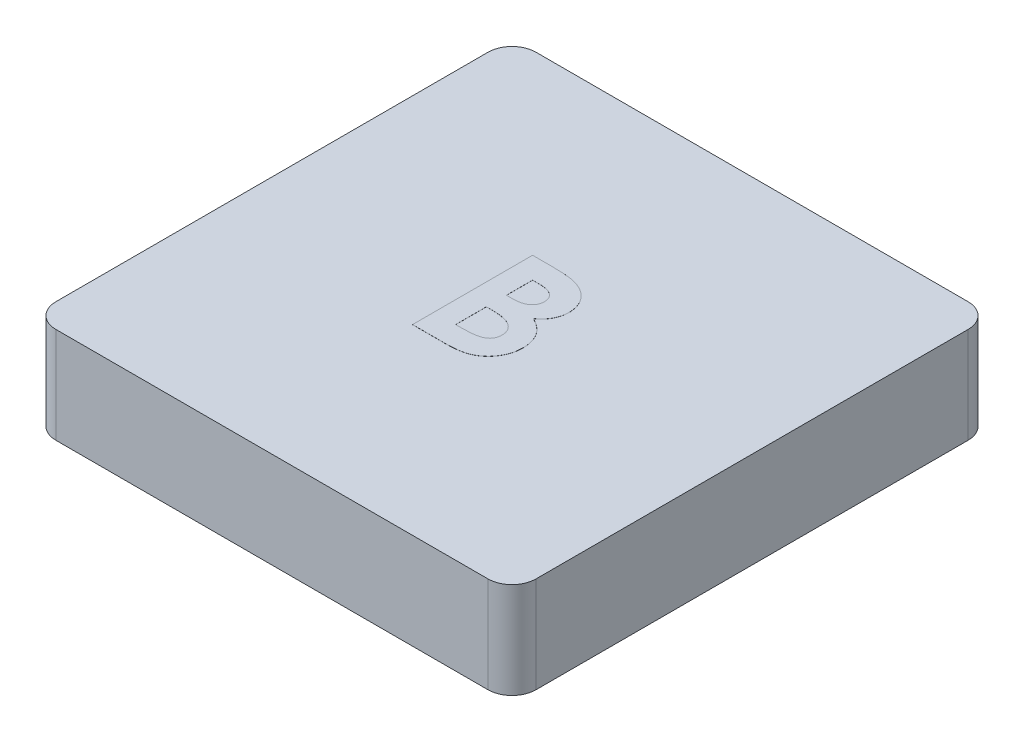
SolidWorks part; units mm, degrees
ref_plane "Front Plane" through (0, 0, 0) normal (0, 0, 1) x (1, 0, 0)
ref_plane "Top Plane" through (0, 0, 0) normal (0, 1, 0) x (1, 0, 0)
ref_plane "Right Plane" through (0, 0, 0) normal (1, 0, 0) x (0, 0, -1)
sketch "Sketch1" plane through (0, 0, 0) normal (0, 1, 0) x (1, 0, 0)
  line L0 (0, 0) -> (12.7, 0)
  line L1 (12.7, 0) -> (12.7, 12.7)
  line L2 (12.7, 12.7) -> (0, 12.7)
  line L3 (0, 12.7) -> (0, 0)
  dimension "D1" = 12.7
  dimension "D2" = 12.7
extrude "Boss-Extrude1" add sketch "Sketch1" along normal blind 2.54
fillet "Fillet1" radius 0.635 4 edges at (0, 1.27, -12.7) (12.7, 1.27, -12.7) (12.7, 1.27, 0) (0, 1.27, 0)
shell "Shell1" thickness 0.635 removed face at (6.35, 0, -6.35)
sketch "Sketch2" plane through (0, 1.905, 0) normal (0, -1, 0) x (-1, 0, 0)
  line L0 (-0.635, 6.35) -> (-12.065, 6.35) construction
  line L1 (-0.635, 12.065) -> (-0.635, 0.635) construction
  line L2 (-12.065, 0.635) -> (-12.065, 12.065) construction
  line L3 (-6.35, 0.635) -> (-6.35, 12.065) construction
  line L4 (-0.635, 0.635) -> (-12.065, 0.635) construction
  line L5 (-12.065, 12.065) -> (-0.635, 12.065) construction
  circle A0 centre (-6.35, 6.35) radius 2.54
  dimension "D1" = 5.08
extrude "Boss-Extrude2" add sketch "Sketch2" along normal up to surface (1.905 mm away) up to face at (6.35, 0, -6.35)
sketch "Sketch3" plane through (0, 2.54, 0) normal (0, 1, 0) x (1, 0, 0)
  line L0 (0, 12.065) -> (0, 0.635) construction
  line L1 (0.635, 0) -> (12.065, 0) construction
  text T0 "<b>B</b>"
  point P1 (0, 0)
  dimension "D1" = 4.8768
  dimension "D2" = 4.826
extrude "Boss-Extrude3" add sketch "Sketch3" along normal blind 0.0025
